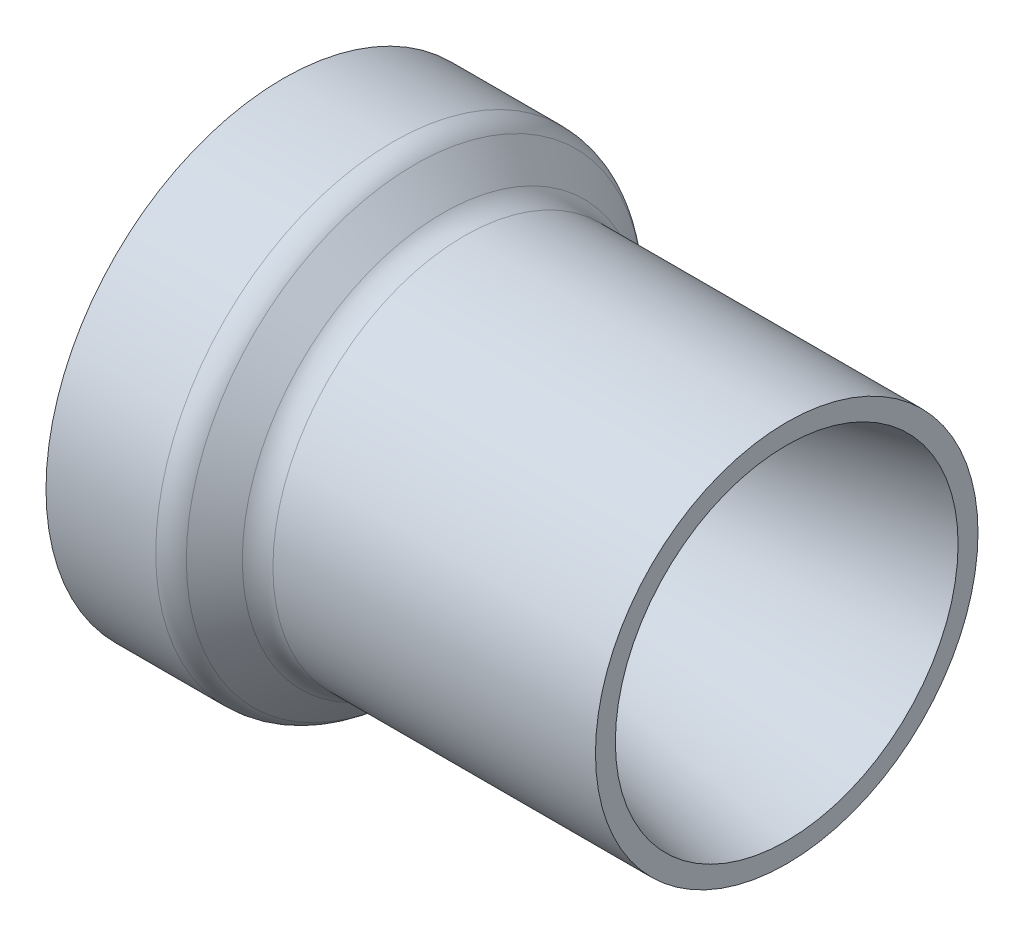
SolidWorks part; units mm, degrees
material "C (Graphite)"
ref_plane "Front Plane" through (0, 0, 0) normal (0, 0, 1) x (1, 0, 0)
ref_plane "Top Plane" through (0, 0, 0) normal (0, 1, 0) x (1, 0, 0)
ref_plane "Right Plane" through (0, 0, 0) normal (1, 0, 0) x (0, 0, -1)
sketch "Sketch1" plane through (0, 0, 0) normal (0, 0, 1) x (1, 0, 0)
  line L0 (0, 0) -> (0, 9.525)
  line L1 (104.4797, 23.1775) -> (20.8314, 40.9575)
  line L2 (0, 9.525) -> (0, 15.875)
  line L3 (0, 58.7375) -> (76.2, 58.7375) construction
  line L5 (14.4814, 40.9575) -> (20.8314, 40.9575)
  line L6 (104.4797, 23.1775) -> (104.4797, 19.05)
  line L7 (22.7697, 9.525) -> (0, 9.525)
  line L9 (27.2599, 11.3849) -> (33.0651, 17.1901)
  line L12 (37.5553, 19.05) -> (104.4797, 19.05)
  line L14 (0, 15.875) -> (14.4814, 40.9575)
  arc A0 (27.2599, 11.3849) -> (22.7697, 9.525) centre (22.7697, 15.875) cw
  arc A1 (37.5553, 19.05) -> (33.0651, 17.1901) centre (37.5553, 12.7) ccw
  point P13 (25.4, 9.525)
  point P17 (34.925, 19.05)
  dimension "D13" = 6.35
  dimension "D14" = 6.35
  dimension "D1" = 58.7375
  dimension "D2" = 60
  dimension "D3" = 6.35
  dimension "D4" = 25.4
  dimension "D5" = 9.525
  dimension "D6" = 9.525
  dimension "D7" = 12
  dimension "D8" = 135
  dimension "D9" = 17.78
  dimension "D10" = 6.35
  dimension "D11" = 69.5547
  dimension "D12" = 35.56
revolve "Revolve1" add sketch "Sketch1" angle 360 about L3 region at (40.045, 24.7674, 0)
